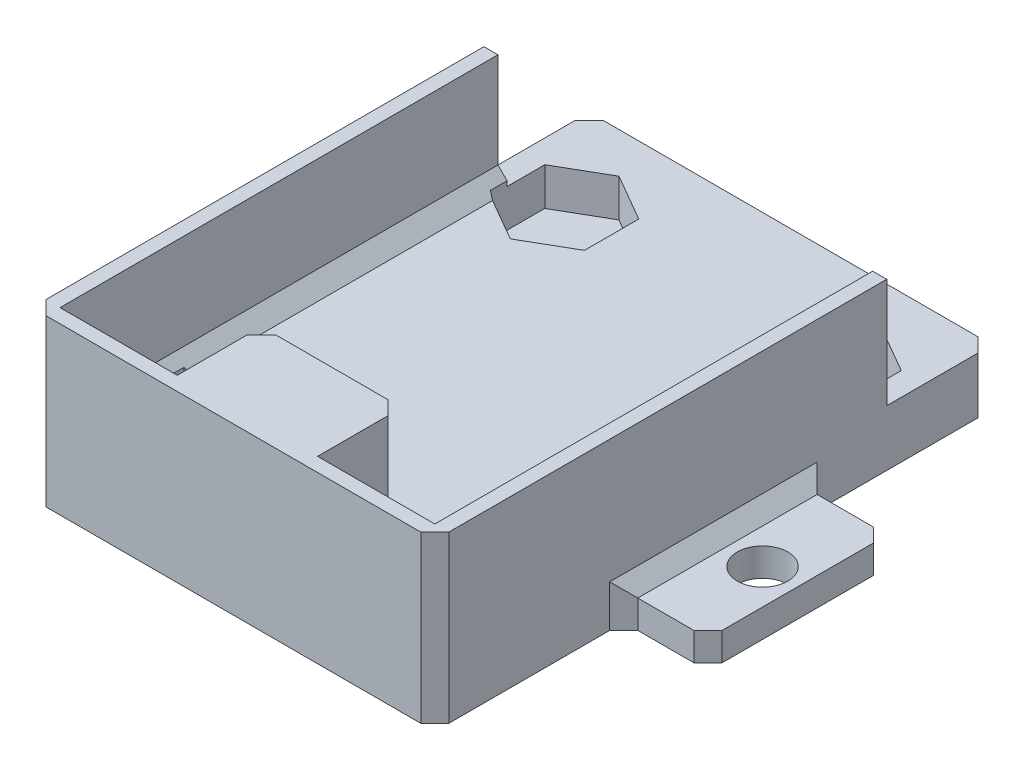
SolidWorks part; units mm, degrees
ref_plane "Front Plane" through (0, 0, 0) normal (0, 0, 1) x (1, 0, 0)
ref_plane "Top Plane" through (0, 0, 0) normal (0, 1, 0) x (1, 0, 0)
ref_plane "Right Plane" through (0, 0, 0) normal (1, 0, 0) x (0, 0, -1)
sketch "Sketch2" plane through (0, 0, 0) normal (0, 1, 0) x (1, 0, 0)
  line L1 (-14.35, -19.85) -> (14.35, -19.85)
  line L2 (-14.35, -19.85) -> (-14.35, 19.85)
  line L3 (-14.35, 19.85) -> (14.35, 19.85)
  line L4 (14.35, -19.85) -> (14.35, 19.85)
  line L5 (-14.35, -19.85) -> (14.35, 19.85) construction
  line L6 (-14.35, 19.85) -> (14.35, -19.85) construction
  point P0 (0, 0)
  dimension "D1" = 39.7
  dimension "D2" = 28.7
extrude "Boss-Extrude1" add sketch "Sketch2" along normal blind 10.8
sketch "Sketch3" plane through (0, 10.8, 0) normal (0, 1, 0) x (1, 0, 0)
  line L1 (-13.35, -18.85) -> (13.35, -18.85)
  line L2 (-13.35, -18.85) -> (-13.35, 18.85)
  line L3 (-13.35, 18.85) -> (13.35, 18.85)
  line L4 (13.35, -18.85) -> (13.35, 18.85)
  line L5 (-13.35, -18.85) -> (13.35, 18.85) construction
  line L6 (-13.35, 18.85) -> (13.35, -18.85) construction
  point P0 (0, 0)
  dimension "D1" = 37.7
  dimension "D2" = 26.7
extrude "Cut-Extrude1" cut sketch "Sketch3" against normal blind 7.8
sketch "Sketch4" plane through (14.35, 0, 0) normal (1, 0, 0) x (0, 0, -1)
  line L0 (-19.85, 10.8) -> (19.85, 10.8) construction
  line L1 (19.85, 10.8) -> (19.85, 0) construction
  line L2 (12.35, 3) -> (12.35, 10.8)
  line L3 (12.35, 3) -> (19.85, 3)
  point P0 (12.35, 3)
  dimension "D1" = 7.8
  dimension "D2" = 7.5
extrude "Cut-Extrude2" cut sketch "Sketch4" against normal through all and the other way through all
sketch "Sketch6" plane through (0, 0, 0) normal (0, -1, 0) x (1, 0, 0)
  line L1 (-14.35, -19.85) -> (14.35, -19.85)
  line L2 (-14.35, -19.85) -> (-14.35, 19.85)
  line L3 (-14.35, 19.85) -> (14.35, 19.85)
  line L4 (14.35, -19.85) -> (14.35, 19.85)
  line L5 (-14.35, -19.85) -> (14.35, 19.85) construction
  line L6 (-14.35, 19.85) -> (14.35, -19.85) construction
  point P0 (0, 0)
extrude "Boss-Extrude2" add sketch "Sketch6" along normal blind 1
sketch "Sketch9" plane through (0, 3, 0) normal (0, 1, 0) x (1, 0, 0)
  line L0 (-13.35, 12.35) -> (-13.35, -18.85) construction
  line L1 (-13.35, -18.85) -> (13.35, -18.85) construction
  line L2 (13.35, -18.85) -> (13.35, 12.35) construction
  line L3 (14.35, 19.85) -> (-14.35, 19.85) construction
  line L5 (-9.35, -8.7318) -> (-12.7, -10.6659)
  line L6 (-12.7, -10.6659) -> (-12.7, -14.5341)
  line L7 (-12.7, -14.5341) -> (-9.35, -16.4682)
  line L8 (-9.35, -16.4682) -> (-6, -14.5341)
  line L9 (-6, -14.5341) -> (-6, -10.6659)
  line L10 (-6, -10.6659) -> (-9.35, -8.7318)
  line L11 (9.35, -8.7318) -> (6, -10.6659)
  line L12 (6, -10.6659) -> (6, -14.5341)
  line L13 (6, -14.5341) -> (9.35, -16.4682)
  line L14 (9.35, -16.4682) -> (12.7, -14.5341)
  line L15 (12.7, -14.5341) -> (12.7, -10.6659)
  line L16 (12.7, -10.6659) -> (9.35, -8.7318)
  line L17 (-9.35, 16.9682) -> (-12.7, 15.0341)
  line L18 (-12.7, 15.0341) -> (-12.7, 11.1659)
  line L19 (-12.7, 11.1659) -> (-9.35, 9.2318)
  line L20 (-9.35, 9.2318) -> (-6, 11.1659)
  line L21 (-6, 11.1659) -> (-6, 15.0341)
  line L22 (-6, 15.0341) -> (-9.35, 16.9682)
  line L23 (9.35, 16.9682) -> (6, 15.0341)
  line L24 (6, 15.0341) -> (6, 11.1659)
  line L25 (6, 11.1659) -> (9.35, 9.2318)
  line L26 (9.35, 9.2318) -> (12.7, 11.1659)
  line L27 (12.7, 11.1659) -> (12.7, 15.0341)
  line L28 (12.7, 15.0341) -> (9.35, 16.9682)
  circle A0 centre (-9.35, -12.6) radius 3.35 construction
  circle A1 centre (9.35, -12.6) radius 3.35 construction
  circle A2 centre (-9.35, 13.1) radius 3.35 construction
  circle A3 centre (9.35, 13.1) radius 3.35 construction
  point P0 (-9.35, -12.6)
  point P1 (-9.35, 13.1)
  point P2 (9.35, 13.1)
  point P3 (9.35, -12.6)
  dimension "D1" = 4
  dimension "D2" = 6.25
  dimension "D3" = 4
  dimension "D4" = 6.25
  dimension "D5" = 4
  dimension "D6" = 6.75
  dimension "D7" = 4
  dimension "D8" = 6.75
  dimension "D9" = 6.7
  dimension "D10" = 6.7
  dimension "D11" = 6.7
  dimension "D12" = 6.7
extrude "Cut-Extrude3" cut sketch "Sketch9" against normal blind 2.7 and the other way through all
sketch "Sketch10" plane through (14.35, 0, 0) normal (1, 0, 0) x (0, 0, -1)
  line L0 (19.85, -1) -> (-19.85, -1) construction
  line L1 (-6.3885, 1) -> (6.3885, 1)
  line L2 (-6.3885, 1) -> (-6.3885, -1)
  line L3 (-6.3885, -1) -> (6.3885, -1)
  line L4 (6.3885, 1) -> (6.3885, -1)
  line L5 (-6.3885, 1) -> (6.3885, -1) construction
  line L6 (-6.3885, -1) -> (6.3885, 1) construction
  point P0 (0, 0)
extrude "Boss-Extrude3" add sketch "Sketch10" along normal blind 6
sketch "Sketch11" plane through (0, 1, 0) normal (0, 1, 0) x (1, 0, 0)
  line L0 (20.35, 6.3885) -> (20.35, -6.3885) construction
  circle A0 centre (17.85, 0) radius 1.8
  dimension "D1" = 2.5
extrude "Cut-Extrude4" cut sketch "Sketch11" against normal through all
sketch "Sketch12" plane through (-14.35, 0, 0) normal (-1, 0, 0) x (0, 0, 1)
  line L0 (19.85, -1) -> (-19.85, -1) construction
  line L1 (-6.39, 1) -> (6.39, 1)
  line L2 (-6.39, 1) -> (-6.39, -1)
  line L3 (-6.39, -1) -> (6.39, -1)
  line L4 (6.39, 1) -> (6.39, -1)
  line L5 (-6.39, 1) -> (6.39, -1) construction
  line L6 (-6.39, -1) -> (6.39, 1) construction
  point P0 (0, 0)
  dimension "D1" = 12.78
extrude "Boss-Extrude4" add sketch "Sketch12" along normal blind 6
sketch "Sketch14" plane through (0, 1, 0) normal (0, 1, 0) x (1, 0, 0)
  line L0 (-20.35, -6.39) -> (-20.35, 6.39) construction
  circle A0 centre (-17.85, 0) radius 1.8
  dimension "D1" = 2.5
extrude "Cut-Extrude5" cut sketch "Sketch14" against normal through all
chamfer "Chamfer1" distance 1 angle 45 14 edges at (-20.35, 0, 6.39) (-20.35, 0, -6.39) (-14.35, 0, 6.39) (-14.35, 1, 0) (-14.35, 0, -6.39) (-14.35, 1, -19.85) (14.35, 1, -19.85) (20.35, 0, -6.3885) (20.35, 0, 6.3885) (14.35, 0, -6.3885) (14.35, 1, 0) (14.35, 0, 6.3885) (14.35, 4.9, 19.85) (-14.35, 4.9, 19.85)
sketch "Sketch16" plane through (0, 3, 0) normal (0, 1, 0) x (1, 0, 0)
  line L5 (-13.35, -18.85) -> (13.35, -18.85) construction
  line L6 (-13.35, 12.35) -> (-13.35, -18.85) construction
  line L8 (5, -12.85) -> (-5, -12.85)
  line L9 (5, -12.85) -> (5, -18.85)
  line L10 (5, -18.85) -> (-5, -18.85)
  line L11 (-5, -12.85) -> (-5, -18.85)
  line L12 (5, -12.85) -> (-5, -18.85) construction
  line L13 (5, -18.85) -> (-5, -12.85) construction
  point P0 (0, -15.85)
  point P5 (0, -15.85)
  dimension "D1" = 3
  dimension "D2" = 13.35
  dimension "D3" = 10
  dimension "D4" = 10
extrude "Boss-Extrude5" add sketch "Sketch16" along normal blind 7.8
chamfer "Chamfer2" distance 1 angle 45 6 edges at (13.35, 3, 3.25) (9.175, 3, 18.85) (-13.35, 3, 3.25) (-9.175, 3, 18.85) (-5, 6.9, 12.85) (5, 6.9, 12.85)
